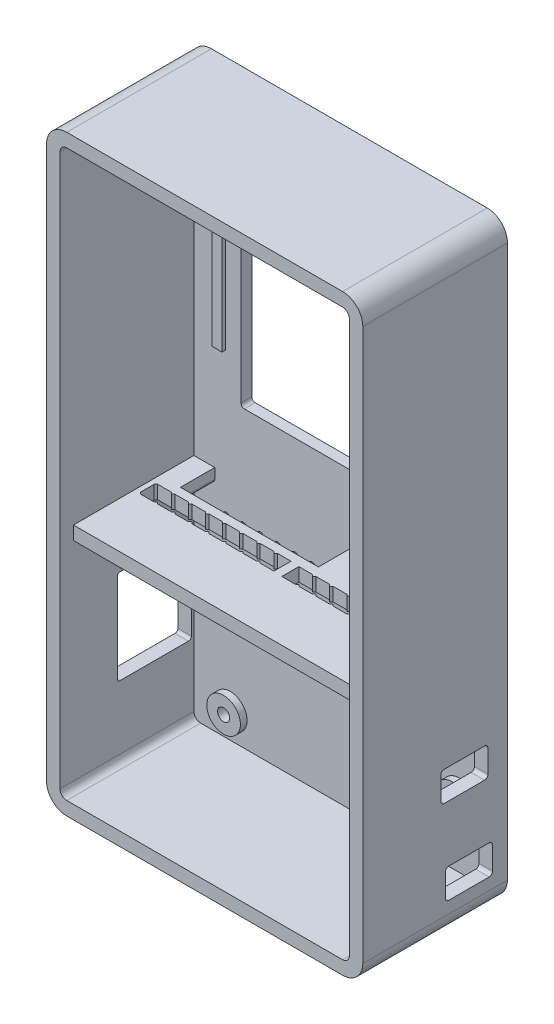
SolidWorks part; units mm, degrees
ref_plane "Front Plane" through (0, 0, 0) normal (0, 0, 1) x (1, 0, 0)
ref_plane "Top Plane" through (0, 0, 0) normal (0, 1, 0) x (1, 0, 0)
ref_plane "Right Plane" through (0, 0, 0) normal (1, 0, 0) x (0, 0, -1)
sketch "Outer_Case_Profile" plane through (0, 0, 0) normal (0, 0, 1) x (1, 0, 0)
  line L1 (-23.5, 44) -> (23.5, 44)
  line L2 (-23.5, 44) -> (-23.5, -44)
  line L3 (-23.5, -44) -> (23.5, -44)
  line L4 (23.5, 44) -> (23.5, -44)
  line L5 (-23.5, 44) -> (23.5, -44) construction
  line L6 (-23.5, -44) -> (23.5, 44) construction
  point P0 (0, 0)
  dimension "D1" = 47
  dimension "D2" = 88
extrude "Outer_Case_Block" add sketch "Outer_Case_Profile" along normal mid plane 21.5
fillet "Outer_Corner_Fillets" radius 3 4 edges at (23.5, -44, 0) (-23.5, -44, 0) (-23.5, 44, 0) (23.5, 44, 0)
sketch "Main_Internal_Cavity_Profile" plane through (0, 0, 10.75) normal (0, 0, 1) x (1, 0, 0)
  line L8 (-20.5, -42) -> (20.5, -42)
  line L9 (21.5, -41) -> (21.5, 41)
  line L10 (20.5, 42) -> (-20.5, 42)
  line L11 (-21.5, 41) -> (-21.5, -41)
  line L12 (-20.5, -42) -> (20.5, -42)
  line L13 (21.5, -41) -> (21.5, 41)
  line L14 (20.5, 42) -> (-20.5, 42)
  line L15 (-21.5, 41) -> (-21.5, -41)
  arc A8 (20.5, -42) -> (21.5, -41) centre (20.5, -41) ccw
  arc A9 (21.5, 41) -> (20.5, 42) centre (20.5, 41) ccw
  arc A10 (-20.5, 42) -> (-21.5, 41) centre (-20.5, 41) ccw
  arc A11 (-21.5, -41) -> (-20.5, -42) centre (-20.5, -41) ccw
  arc A12 (20.5, -42) -> (21.5, -41) centre (20.5, -41) ccw
  arc A13 (21.5, 41) -> (20.5, 42) centre (20.5, 41) ccw
  arc A14 (-20.5, 42) -> (-21.5, 41) centre (-20.5, 41) ccw
  arc A15 (-21.5, -41) -> (-20.5, -42) centre (-20.5, -41) ccw
  dimension "D1" = 2
extrude "Main_Internal_Cavity" cut sketch "Main_Internal_Cavity_Profile" against normal blind 19.9 contours L12 A12 L13 A13 L14 A14 L15 A15
sketch "Component_Layout_Profile" plane through (0, 0, -9.15) normal (0, 0, 1) x (1, 0, 0)
  line L0 (0, -58.7073) -> (0, 65.8161) construction
  line L2 (-16.8, -8.1) -> (16.8, -8.1) construction
  line L3 (-16.8, -8.1) -> (-16.8, 40.5) construction
  line L4 (-16.8, 40.5) -> (16.8, 40.5) construction
  line L5 (16.8, -8.1) -> (16.8, 40.5) construction
  line L6 (-16.8, -8.1) -> (16.8, 40.5) construction
  line L7 (-16.8, 40.5) -> (16.8, -8.1) construction
  line L10 (20.5, 42) -> (-20.5, 42) construction
  line L12 (19.25, -10.75) -> (-19.25, -10.75)
  line L13 (19.25, -10.75) -> (19.25, -41.25)
  line L14 (19.25, -41.25) -> (-19.25, -41.25)
  line L15 (-19.25, -10.75) -> (-19.25, -41.25)
  line L16 (19.25, -10.75) -> (-19.25, -41.25) construction
  line L17 (19.25, -41.25) -> (-19.25, -10.75) construction
  line L18 (-20.5, -42) -> (20.5, -42) construction
  point P3 (0, 16.2)
  point P15 (0, -26)
  dimension "D1" = 48.6
  dimension "D2" = 33.6
  dimension "D3" = 1.5
  dimension "D4" = 38.5
  dimension "D5" = 30.5
  dimension "D6" = 0.75
sketch "Display_Window_Profile" plane through (0, 0, -9.15) normal (0, 0, 1) x (1, 0, 0)
  line L0 (0, -58.7073) -> (0, 65.8161)
  line L1 (14, 30.7) -> (-14, 30.7)
  line L2 (14.5, 30.2) -> (14.5, 2.2)
  line L3 (14, 1.7) -> (-14, 1.7)
  line L4 (-14.5, 30.2) -> (-14.5, 2.2)
  line L5 (14.5, 30.7) -> (-14.5, 1.7) construction
  line L6 (14.5, 1.7) -> (-14.5, 30.7) construction
  line L7 (0, -58.7073) -> (0, 65.8161) construction
  arc A0 (14, 1.7) -> (14.5, 2.2) centre (14, 2.2) ccw
  arc A1 (-14, 30.7) -> (-14.5, 30.2) centre (-14, 30.2) ccw
  arc A2 (14.5, 30.2) -> (14, 30.7) centre (14, 30.2) ccw
  arc A3 (-14.5, 2.2) -> (-14, 1.7) centre (-14, 2.2) ccw
  point P0 (0, 16.2)
  dimension "D4" = 0.5
  dimension "D1" = 29
  dimension "D2" = 29
  dimension "D3" = 16.2
extrude "Display_Window_Cut" cut sketch "Display_Window_Profile" against normal through all contours A2 L1 A1 L4 A3 L3 A0 L2
sketch "Display_Support_Rails_Profile" plane through (0, 0, -9.15) normal (0, 0, 1) x (1, 0, 0)
  line L0 (0, 16.2) -> (46.5944, 16.2) construction
  line L2 (18.3, 38.2) -> (16.8, 38.2)
  line L3 (18.3, 38.2) -> (18.3, -5.8)
  line L4 (18.3, -5.8) -> (16.8, -5.8)
  line L5 (16.8, 38.2) -> (16.8, -5.8)
  line L6 (18.3, 38.2) -> (16.8, -5.8) construction
  line L7 (18.3, -5.8) -> (16.8, 38.2) construction
  line L8 (0, 65.8161) -> (0, -58.7073) construction
  line L9 (-18.3, -5.8) -> (-16.8, 38.2) construction
  line L10 (-18.3, 38.2) -> (-16.8, -5.8) construction
  line L11 (-16.8, 38.2) -> (-16.8, -5.8)
  line L12 (-18.3, -5.8) -> (-16.8, -5.8)
  line L13 (-18.3, 38.2) -> (-18.3, -5.8)
  line L14 (-18.3, 38.2) -> (-16.8, 38.2)
  point P2 (17.55, 16.2)
  point P16 (-17.55, 16.2)
  dimension "D1" = 1.5
  dimension "D2" = 44
  dimension "D3" = 33.6
extrude "Display_Support_Rails" add sketch "Display_Support_Rails_Profile" along normal mid plane 1
sketch "Separator_Profile" plane through (0, 0, -9.15) normal (0, 0, 1) x (1, 0, 0)
  line L1 (21.5, -8.05) -> (-21.5, -8.05)
  line L2 (21.5, -8.05) -> (21.5, -10.05)
  line L3 (21.5, -10.05) -> (-21.5, -10.05)
  line L4 (-21.5, -8.05) -> (-21.5, -10.05)
  line L5 (21.5, -8.05) -> (-21.5, -10.05) construction
  line L6 (21.5, -10.05) -> (-21.5, -8.05) construction
  line L8 (0, -58.7073) -> (0, 65.8161) construction
  line L16 (-16.8, -8.1) -> (16.8, -8.1) construction
  line L18 (21.5, -41) -> (21.5, 41) construction
  point P0 (0, -9.05)
  point P9 (21.5, -8.8332)
  dimension "D2" = 0.05
extrude "Separator_Rib" add sketch "Separator_Profile" along normal blind 17.9
sketch "Display_Cable_Slot_Profile" plane through (0, -10.05, 0) normal (0, -1, 0) x (1, 0, 0)
  line L0 (-21.5, -9.15) -> (21.5, -9.15) construction
  line L5 (-18.4, -4.05) -> (2.1, -4.05)
  line L6 (-18.4, -4.05) -> (-18.4, -9.15)
  line L7 (-18.4, -9.15) -> (2.1, -9.15)
  line L8 (-21.5, 8.75) -> (-21.5, -9.15) construction
  line L9 (2.1, -4.05) -> (2.1, -9.15)
  line L10 (-18.4, -4.05) -> (2.1, -9.15) construction
  line L11 (-18.4, -9.15) -> (2.1, -4.05) construction
  line L12 (0, 4.6) -> (0, -30.3967) construction
  line L13 (-0.6794, -0.215) -> (-2.7114, -0.215)
  line L14 (-2.7114, -0.215) -> (-2.9654, -0.469)
  line L15 (-2.9654, -0.469) -> (-3.2194, -0.215)
  line L16 (-3.2194, -0.215) -> (-5.2514, -0.215)
  line L17 (-5.2514, -0.215) -> (-5.5054, -0.469)
  line L18 (-5.5054, -0.469) -> (-5.7594, -0.215)
  line L19 (-5.7594, -0.215) -> (-7.7914, -0.215)
  line L20 (-7.7914, -0.215) -> (-8.0454, -0.469)
  line L21 (-8.0454, -0.469) -> (-8.2994, -0.215)
  line L22 (-8.2994, -0.215) -> (-10.3314, -0.215)
  line L23 (-10.3314, -0.215) -> (-10.5854, -0.469)
  line L24 (-10.5854, -0.469) -> (-10.8394, -0.215)
  line L25 (-10.8394, -0.215) -> (-12.8714, -0.215)
  line L26 (-12.8714, -0.215) -> (-13.1254, -0.469)
  line L27 (-13.1254, -0.469) -> (-13.3794, -0.215)
  line L28 (-13.3794, -0.215) -> (-15.4114, -0.215)
  line L29 (-15.4114, -0.215) -> (-15.6654, -0.469)
  line L30 (-15.6654, -0.469) -> (-15.9194, -0.215)
  line L31 (-15.9194, -0.215) -> (-17.9514, -0.215)
  line L32 (-17.9514, -0.215) -> (-18.2054, -0.469)
  line L33 (-18.2054, -0.469) -> (-18.4594, -0.215)
  line L34 (-18.4594, -0.215) -> (-20.4914, -0.215)
  line L35 (-20.4914, -0.215) -> (-20.7454, -0.469)
  line L36 (-20.7454, -0.469) -> (-20.7454, -2.501)
  line L37 (-20.7454, -2.501) -> (-20.4914, -2.755)
  line L38 (-20.4914, -2.755) -> (-18.4594, -2.755)
  line L39 (-18.4594, -2.755) -> (-18.2054, -2.501)
  line L40 (-18.2054, -2.501) -> (-17.9514, -2.755)
  line L41 (-17.9514, -2.755) -> (-15.9194, -2.755)
  line L42 (-15.9194, -2.755) -> (-15.6654, -2.501)
  line L43 (-15.6654, -2.501) -> (-15.4114, -2.755)
  line L44 (-15.4114, -2.755) -> (-13.3794, -2.755)
  line L45 (-13.3794, -2.755) -> (-13.1254, -2.501)
  line L46 (-13.1254, -2.501) -> (-12.8714, -2.755)
  line L47 (-12.8714, -2.755) -> (-10.8394, -2.755)
  line L48 (-10.8394, -2.755) -> (-10.5854, -2.501)
  line L49 (-10.5854, -2.501) -> (-10.3314, -2.755)
  line L50 (-10.3314, -2.755) -> (-8.2994, -2.755)
  line L51 (-8.2994, -2.755) -> (-8.0454, -2.501)
  line L52 (-8.0454, -2.501) -> (-7.7914, -2.755)
  line L53 (-7.7914, -2.755) -> (-5.7594, -2.755)
  line L54 (-5.7594, -2.755) -> (-5.5054, -2.501)
  line L55 (-5.5054, -2.501) -> (-5.2514, -2.755)
  line L56 (-5.2514, -2.755) -> (-3.2194, -2.755)
  line L57 (-3.2194, -2.755) -> (-2.9654, -2.501)
  line L58 (-2.9654, -2.501) -> (-2.7114, -2.755)
  line L59 (-2.7114, -2.755) -> (-0.6794, -2.755)
  line L60 (-0.6794, -0.215) -> (-0.6794, -2.755)
  line L61 (0.6071, -2.6518) -> (2.6391, -2.6518)
  line L62 (2.6391, -2.6518) -> (2.8931, -2.3978)
  line L63 (2.8931, -2.3978) -> (3.1471, -2.6518)
  line L64 (3.1471, -2.6518) -> (5.1791, -2.6518)
  line L65 (5.1791, -2.6518) -> (5.4331, -2.3978)
  line L66 (5.4331, -2.3978) -> (5.6871, -2.6518)
  line L67 (5.6871, -2.6518) -> (7.7191, -2.6518)
  line L68 (7.7191, -2.6518) -> (7.9731, -2.3978)
  line L69 (7.9731, -2.3978) -> (8.2271, -2.6518)
  line L70 (8.2271, -2.6518) -> (10.2591, -2.6518)
  line L71 (10.2591, -2.6518) -> (10.5131, -2.3978)
  line L72 (10.5131, -2.3978) -> (10.7671, -2.6518)
  line L73 (10.7671, -2.6518) -> (12.7991, -2.6518)
  line L74 (12.7991, -2.6518) -> (13.0531, -2.3978)
  line L75 (13.0531, -2.3978) -> (13.3071, -2.6518)
  line L76 (13.3071, -2.6518) -> (15.3391, -2.6518)
  line L77 (15.3391, -2.6518) -> (15.5931, -2.3978)
  line L78 (15.5931, -2.3978) -> (15.8471, -2.6518)
  line L79 (15.8471, -2.6518) -> (17.8791, -2.6518)
  line L80 (17.8791, -2.6518) -> (18.1331, -2.3978)
  line L81 (18.1331, -2.3978) -> (18.3871, -2.6518)
  line L82 (18.3871, -2.6518) -> (20.4191, -2.6518)
  line L83 (20.4191, -2.6518) -> (20.6731, -2.3978)
  line L84 (20.6731, -2.3978) -> (20.6731, -0.3658)
  line L85 (20.6731, -0.3658) -> (20.4191, -0.1118)
  line L86 (20.4191, -0.1118) -> (18.3871, -0.1118)
  line L87 (18.3871, -0.1118) -> (18.1331, -0.3658)
  line L88 (18.1331, -0.3658) -> (17.8791, -0.1118)
  line L89 (17.8791, -0.1118) -> (15.8471, -0.1118)
  line L90 (15.8471, -0.1118) -> (15.5931, -0.3658)
  line L91 (15.5931, -0.3658) -> (15.3391, -0.1118)
  line L92 (15.3391, -0.1118) -> (13.3071, -0.1118)
  line L93 (13.3071, -0.1118) -> (13.0531, -0.3658)
  line L94 (13.0531, -0.3658) -> (12.7991, -0.1118)
  line L95 (12.7991, -0.1118) -> (10.7671, -0.1118)
  line L96 (10.7671, -0.1118) -> (10.5131, -0.3658)
  line L97 (10.5131, -0.3658) -> (10.2591, -0.1118)
  line L98 (10.2591, -0.1118) -> (8.2271, -0.1118)
  line L99 (8.2271, -0.1118) -> (7.9731, -0.3658)
  line L100 (7.9731, -0.3658) -> (7.7191, -0.1118)
  line L101 (7.7191, -0.1118) -> (5.6871, -0.1118)
  line L102 (5.6871, -0.1118) -> (5.4331, -0.3658)
  line L103 (5.4331, -0.3658) -> (5.1791, -0.1118)
  line L104 (5.1791, -0.1118) -> (3.1471, -0.1118)
  line L105 (3.1471, -0.1118) -> (2.8931, -0.3658)
  line L106 (2.8931, -0.3658) -> (2.6391, -0.1118)
  line L107 (2.6391, -0.1118) -> (0.6071, -0.1118)
  line L108 (0.6071, -2.6518) -> (0.6071, -0.1118)
  point P0 (-8.15, -6.6)
  point P5 (-6.7299, -4.05)
  point P8 (-2.475, -9.15)
  dimension "D1" = 20.5
  dimension "D2" = 5.1
  dimension "D3" = 3.1
extrude "Display_Cable_Slot_cut" cut sketch "Display_Cable_Slot_Profile" against normal blind 17.9
fillet "Cable_Slot_Fillets" radius 0.5 2 edges at (2.1, -10.05, -6.6) (-18.4, -10.05, -6.6)
sketch "PCB_Mounting_Bosses_Profile" plane through (0, 0, -9.15) normal (0, 0, 1) x (1, 0, 0)
  line L1 (19.25, -10.75) -> (19.25, -41.25) construction
  line L2 (19.25, -10.75) -> (-19.25, -10.75) construction
  circle A0 centre (-16.09, -38.215) radius 2.5
  circle A1 centre (17.13, -12.87) radius 2.5
  circle A2 centre (17.9, -32.345) radius 2.5
  dimension "D2" = 5
  dimension "D3" = 5
  dimension "D4" = 2.12
  dimension "D5" = 2.12
  dimension "D6" = 33.22
  dimension "D7" = 25.345
  dimension "D8" = 33.99
  dimension "D9" = 5.87
extrude "PCB_Mounting_Bosses" add sketch "PCB_Mounting_Bosses_Profile" along normal mid plane 2
sketch "PCB_Boss_Pilot_Holes_profile" plane through (0, 0, -8.15) normal (0, 0, 1) x (1, 0, 0)
  circle A0 centre (17.9, -32.345) radius 0.9
  circle A1 centre (-16.09, -38.215) radius 0.9
  circle A2 centre (17.13, -12.87) radius 0.9
  circle A4 centre (17.13, -12.87) radius 2.5 construction
  circle A5 centre (17.9, -32.345) radius 2.5 construction
  circle A6 centre (-16.09, -38.215) radius 2.5 construction
  dimension "D2" = 1.8
  dimension "D3" = 1.8
extrude "PCB_Boss_Pilot_Holes" cut sketch "PCB_Boss_Pilot_Holes_profile" against normal blind 2
sketch "Sketch3" plane through (0, 0, -10.75) normal (0, 0, -1) x (-1, 0, 0)
  line L0 (-19.25, -10.75) -> (-19.25, -41.25) construction
  line L2 (-19.25, -10.75) -> (19.25, -10.75) construction
  circle A0 centre (1.4035, -13.4537) radius 0.502
  circle A1 centre (3.9535, -13.4537) radius 0.502
  circle A3 centre (-1.1465, -13.4537) radius 0.502
  circle A4 centre (6.5035, -13.4537) radius 0.502
  circle A5 centre (9.0535, -13.4537) radius 0.502
  circle A6 centre (11.6035, -13.4537) radius 0.502
  circle A7 centre (14.1535, -13.4537) radius 0.502
  circle A8 centre (16.7035, -13.4537) radius 0.502
  dimension "D3" = 2.7037
  dimension "D1" = 18.1035
  dimension "D2" = 8
extrude "Cut-Extrude3" cut sketch "Sketch3" against normal up to next and the other way blind 0.3
sketch "Sketch1" plane through (0, 0, -10.75) normal (0, 0, -1) x (-1, 0, 0)
  line L0 (20.29, -13.43) -> (21.7526, -13.43) construction
  line L6 (21.7526, -13.43) -> (17.9452, -13.43) construction
  circle M58 centre (16.7035, -13.4537) radius 0.502
  circle M59 centre (14.1535, -13.4537) radius 0.502
  circle M60 centre (11.6035, -13.4537) radius 0.502
  circle M61 centre (9.0535, -13.4537) radius 0.502
  circle M62 centre (6.5035, -13.4537) radius 0.502
  circle M63 centre (3.9535, -13.4537) radius 0.502
  circle M64 centre (-1.1465, -13.4537) radius 0.502
  circle M65 centre (1.4035, -13.4537) radius 0.502
extrude "Boss-Extrude3" add sketch "Sketch1" along normal blind 0.5 separate body contours M64 | M65 | M63 | M62 | M61 | M60 | M59 | M58 region at (-16.7035, -13.4537, -10.75) region at (-14.1535, -13.4537, -10.75) region at (-11.6035, -13.4537, -10.75) region at (-9.0535, -13.4537, -10.75) region at (-6.5035, -13.4537, -10.75) region at (-3.9535, -13.4537, -10.75) region at (1.1465, -13.4537, -10.75) region at (-1.4035, -13.4537, -10.75)
sketch "Sketch4" plane through (0, 0, -9.15) normal (0, 0, 1) x (1, 0, 0)
  line L0 (13.0921, -18.279) -> (15.3084, -18.279)
  line L9 (13.0921, -18.279) -> (13.0921, -19.979)
  line L10 (15.6684, -18.1937) -> (17.8847, -18.1937)
  line L11 (15.6684, -18.1937) -> (15.6684, -19.8937)
  line L12 (15.6684, -19.8937) -> (17.8847, -19.8937)
  line L13 (17.8847, -18.1937) -> (17.8847, -19.8937)
  line L14 (15.6684, -18.1937) -> (17.8847, -19.8937) construction
  line L15 (15.6684, -19.8937) -> (17.8847, -18.1937) construction
  line L16 (13.0921, -19.979) -> (15.3084, -19.979)
  line L17 (15.3084, -18.279) -> (15.3084, -19.979)
  line L18 (13.0921, -18.279) -> (15.3084, -19.979) construction
  line L19 (13.0921, -19.979) -> (15.3084, -18.279) construction
  line L20 (21.5, -41) -> (21.5, 41) construction
  line L21 (14.5, 30.2) -> (14.5, 2.2) construction
  line L22 (-21.5, -10.05) -> (-18.9, -10.05) construction
  line L23 (14, 30.7) -> (-14, 30.7) construction
  point P0 (17.1311, -12.8837)
  point P1 (16.7766, -19.0437)
  point P6 (0, 0)
  point P7 (14.2003, -19.129)
  dimension "D1" = 1.7
  dimension "D2" = 6.16
  dimension "D3" = 0.36
  dimension "D4" = 3.6153
  dimension "D5" = 0.8084
  dimension "D6" = 48.979
extrude "Cut-Extrude4" cut sketch "Sketch4" against normal up to next (1.6 mm away) contours L13 L10 L11 L12 | L17 L0 L9 L16
extrude "Boss-Extrude4" add sketch "Sketch4<3>" against normal blind 1 from offset 1.1 offset against normal yes
sketch "Sketch4<3>" plane through (0, 0, -9.15) normal (0, 0, 1) x (1, 0, 0) same geometry as "Sketch4"
sketch "Sketch5" plane through (21.5, 0, 0) normal (-1, 0, 0) x (0, 0, 1)
  line L0 (-1.3499, -26.4426) -> (-7.3499, -26.4426)
  line L1 (-2.021, -39.2382) -> (-8.021, -39.2382)
  line L2 (-1.521, -38.7382) -> (-1.521, -35.3382)
  line L3 (-2.021, -34.8382) -> (-8.021, -34.8382)
  line L4 (-8.521, -38.7382) -> (-8.521, -35.3382)
  line L5 (-1.521, -39.2382) -> (-8.521, -34.8382) construction
  line L6 (-1.521, -34.8382) -> (-8.521, -39.2382) construction
  line L7 (-0.8499, -25.9426) -> (-0.8499, -22.5426)
  line L8 (-1.3499, -22.0426) -> (-7.3499, -22.0426)
  line L9 (-7.8499, -25.9426) -> (-7.8499, -22.5426)
  arc A0 (-8.521, -38.7382) -> (-8.021, -39.2382) centre (-8.021, -38.7382) ccw
  arc A1 (-2.021, -39.2382) -> (-1.521, -38.7382) centre (-2.021, -38.7382) ccw
  arc A2 (-1.521, -35.3382) -> (-2.021, -34.8382) centre (-2.021, -35.3382) ccw
  arc A3 (-8.021, -34.8382) -> (-8.521, -35.3382) centre (-8.021, -35.3382) ccw
  arc A4 (-0.8499, -25.9426) -> (-1.3499, -26.4426) centre (-1.3499, -25.9426) cw
  arc A5 (-0.8499, -22.5426) -> (-1.3499, -22.0426) centre (-1.3499, -22.5426) ccw
  arc A6 (-7.8499, -22.5426) -> (-7.3499, -22.0426) centre (-7.3499, -22.5426) cw
  arc A7 (-7.3499, -26.4426) -> (-7.8499, -25.9426) centre (-7.3499, -25.9426) cw
  point P0 (-5.021, -37.0382)
  point P5 (0, 0)
  point P6 (-13.7075, -39.762)
  point P7 (-6.3285, -37.4559)
  point P8 (-5.055, -37.0344)
  dimension "D3" = 0.5
  dimension "D1" = 4.4
  dimension "D2" = 7
extrude "Cut-Extrude5" cut sketch "Sketch5" against normal up to next (2 mm away)
sketch "Sketch6" plane through (-21.5, 0, 0) normal (1, 0, 0) x (0, 0, -1)
  line L0 (-1.8185, -17.5388) -> (8.3447, -17.5388)
  line L1 (-2.2369, -17.9572) -> (-2.2369, -31.1204)
  line L2 (-1.8185, -31.5388) -> (8.3447, -31.5388)
  line L3 (8.7631, -17.9572) -> (8.7631, -31.1204)
  line L4 (-2.2369, -17.5388) -> (8.7631, -31.5388) construction
  line L5 (-2.2369, -31.5388) -> (8.7631, -17.5388) construction
  arc A0 (8.7631, -17.9572) -> (8.3447, -17.5388) centre (8.3447, -17.9572) ccw
  arc A1 (8.3447, -31.5388) -> (8.7631, -31.1204) centre (8.3447, -31.1204) ccw
  arc A2 (-1.8185, -31.5388) -> (-2.2369, -31.1204) centre (-1.8185, -31.1204) cw
  arc A3 (-2.2369, -17.9572) -> (-1.8185, -17.5388) centre (-1.8185, -17.9572) cw
  point P0 (3.2631, -24.5388)
  point P17 (1.8825, -26.2779)
extrude "Cut-Extrude6" cut sketch "Sketch6" against normal up to next (2 mm away)
equation "\"pcb_w\"= 38mm"
equation "\"pcb_h\"= 30mm"
equation "\"pcb_t\"= 1.6mm"
equation "\"pcb_clr\"= .25mm"
equation "\"pcb_pocket_h\"= 30.5mm"
equation "\"pcb_pocket_w\"= 38.5mm"
equation "\"disp_l\"= 48mm"
equation "\"disp_w\"= 33mm"
equation "\"disp_pocket_l\"= 48.6mm"
equation "\"disp_pocket_w\"= 33.6mm"
equation "\"disp_clr\"= .3mm"
equation "\"active\"= 27.6mm"
equation "\"win\"= 29mm"
equation "\"disp_total_t\"= 6mm"
equation "\"glass_front_gap\"= .4mm"
equation "\"foam_front\"= 1mm"
equation "\"foam_back\"= 2mm"
equation "\"wall\"= 2mm"
equation "\"front_wall\"= 1.6mm"
equation "\"base_t\"= 2mm"
equation "\"sep_t\"= 2mm"
equation "\"ceiling_clr\"= 1mm"
equation "\"boss_od\"= 5mm"
equation "\"boss_h\"= 2mm"
equation "\"boss_pilot\"= 1.8mm"
equation "\"socket_h\"= 8.5mm"
equation "\"sn_t\"= 1mm"
equation "\"usb_h\"= 3.4mm"
equation "\"usb_overhang\"= 2mm"
equation "\"usb_gap\"= .3mm"
equation "\"pin_tip\"= 0mm"
equation "\"batt_l\"= 35mm"
equation "\"batt_w\"= 25mm"
equation "\"batt_t\"= 5mm"
equation "\"batt_clr\"= 1mm"
equation "\"battery_depth_add\"= 1.5"
equation "\"sw_z\"= 7.4mm"
equation "\"sw_pitch\"= 0"
equation "\"antenna_clearance\"= 8mm"
equation "\"right_gap\"= 2mm"
equation "\"case_w\"= 47mm"
equation "\"case_h\"= 88mm"
equation "\"case_d\"= 21.5mm"
equation "\"D1@Outer_Case_Profile\" = \"case_w\""
equation "\"D2@Outer_Case_Profile\" = \"case_h\""
equation "\"D1@Outer_Case_Block\" = \"case_d\""
equation "\"D1@Main_Internal_Cavity\" = \"case_d\" - \"front_wall\""
equation "\"D1@Component_Layout_Profile\" = \"disp_pocket_l\""
equation "\"D2@Component_Layout_Profile\" = \"disp_pocket_w\""
equation "\"D4@Component_Layout_Profile\" = \"pcb_pocket_w\""
equation "\"D5@Component_Layout_Profile\" = \"pcb_pocket_h\""
equation "\"D1@Display_Window_Profile\"=\"win\""
equation "\"D2@Display_Window_Profile\"=\"win\""
equation "\"D3@Display_Window_Profile\"=\"case_h\"/2 - \"wall\" - 1.5mm - \"disp_pocket_l\"/2"
equation "\"D3@Display_Support_Rails_Profile\" = \"disp_pocket_w\""
equation "\"D1@Separator_Profile\"=\"sep_t\""
equation "\"D1@Separator_Rib\" = \"case_d\" - \"front_wall\" - \"base_t\""
equation "\"D1@Display_Cable_Slot_cut\"=\"case_d\" - \"front_wall\" - \"base_t\""
equation "\"D1@PCB_Mounting_Bosses_Profile\" = \"boss_od\""
equation "\"D2@PCB_Mounting_Bosses_Profile\" = \"boss_od\""
equation "\"D3@PCB_Mounting_Bosses_Profile\" = \"boss_od\""
equation "\"D1@PCB_Mounting_Bosses\"=\"boss_h\""
equation "\"D1@PCB_Boss_Pilot_Holes_profile\" = \"boss_pilot\""
equation "\"D2@PCB_Boss_Pilot_Holes_profile\" = \"boss_pilot\""
equation "\"D3@PCB_Boss_Pilot_Holes_profile\" = \"boss_pilot\""
equation "\"D1\" = \"boss_h\""
equation "\"D1@PCB_Boss_Pilot_Holes\" = \"boss_h\""
